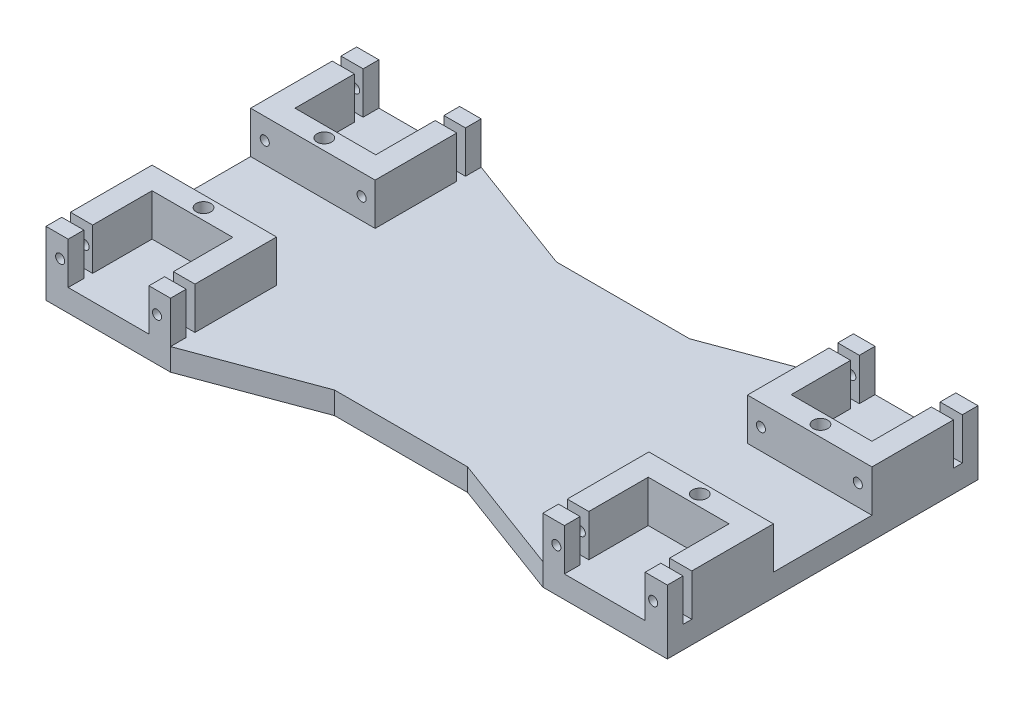
SolidWorks part; units mm, degrees
ref_plane "Front Plane" through (0, 0, 0) normal (0, 0, 1) x (1, 0, 0)
ref_plane "Top Plane" through (0, 0, 0) normal (0, 1, 0) x (1, 0, 0)
ref_plane "Right Plane" through (0, 0, 0) normal (1, 0, 0) x (0, 0, -1)
sketch "Sketch2" plane through (0, 0, 0) normal (0, 1, 0) x (1, 0, 0)
  line L0 (88.9, 0) -> (88.9, 88.9) construction
  line L1 (0, 0) -> (177.8, 0)
  line L2 (0, 0) -> (0, 88.9)
  line L3 (0, 88.9) -> (177.8, 88.9)
  line L4 (177.8, 0) -> (177.8, 88.9)
  line L5 (44.45, 12.7) -> (133.35, 12.7) construction
  line L6 (44.45, 12.7) -> (44.45, 76.2) construction
  line L7 (44.45, 76.2) -> (133.35, 76.2) construction
  line L8 (133.35, 12.7) -> (133.35, 76.2) construction
  line L9 (171.45, 0) -> (148.336, 0)
  line L10 (171.45, 0) -> (171.45, 23.9979)
  line L11 (171.45, 23.9979) -> (148.336, 23.9979)
  line L12 (148.336, 0) -> (148.336, 23.9979)
  line L13 (142.171, 30.3479) -> (177.8, 30.3479)
  line L14 (142.171, 30.3479) -> (142.171, -6.35)
  line L15 (142.171, -6.35) -> (177.8, -6.35)
  line L16 (177.8, 30.3479) -> (177.8, -6.35)
  line L17 (142.171, 30.3479) -> (177.8, -6.35) construction
  line L18 (142.171, -6.35) -> (177.8, 30.3479) construction
  line L19 (0, 44.45) -> (177.8, 44.45) construction
  line L20 (35.629, -6.35) -> (0, -6.35)
  line L21 (0, 30.3479) -> (0, -6.35)
  line L22 (35.629, 30.3479) -> (0, 30.3479)
  line L23 (35.629, 30.3479) -> (35.629, -6.35)
  line L24 (6.35, 23.9979) -> (29.464, 23.9979)
  line L25 (29.464, 0) -> (29.464, 23.9979)
  line L26 (6.35, 0) -> (29.464, 0)
  line L27 (6.35, 0) -> (6.35, 23.9979)
  line L28 (171.45, 64.9021) -> (148.336, 64.9021)
  line L29 (148.336, 88.9) -> (148.336, 64.9021)
  line L30 (171.45, 88.9) -> (148.336, 88.9)
  line L31 (171.45, 88.9) -> (171.45, 64.9021)
  line L32 (142.171, 95.25) -> (177.8, 95.25)
  line L33 (177.8, 58.5521) -> (177.8, 95.25)
  line L34 (142.171, 58.5521) -> (177.8, 58.5521)
  line L35 (142.171, 58.5521) -> (142.171, 95.25)
  line L36 (6.35, 88.9) -> (6.35, 64.9021)
  line L37 (6.35, 88.9) -> (29.464, 88.9)
  line L38 (29.464, 88.9) -> (29.464, 64.9021)
  line L39 (6.35, 64.9021) -> (29.464, 64.9021)
  line L40 (35.629, 58.5521) -> (35.629, 95.25)
  line L41 (35.629, 58.5521) -> (0, 58.5521)
  line L42 (0, 58.5521) -> (0, 95.25)
  line L43 (35.629, 95.25) -> (0, 95.25)
  line L44 (35.629, 0) -> (69.85, 12.7)
  line L45 (69.85, 12.7) -> (107.95, 12.7)
  line L46 (107.95, 12.7) -> (142.171, 0)
  line L47 (35.629, 88.9) -> (69.85, 76.2)
  line L48 (69.85, 76.2) -> (107.95, 76.2)
  line L49 (107.95, 76.2) -> (142.171, 88.9)
  point P9 (159.9855, 11.999)
  dimension "D1" = 88.9
  dimension "D2" = 177.8
  dimension "D3" = 63.5
  dimension "D4" = 88.9
  dimension "D5" = 31.75
  dimension "D6" = 23.114
  dimension ".9448" = 23.9979
  dimension "D7" = 6.35
  dimension "D8" = 6.35
  dimension "D9" = 44.45
  dimension "D10" = 38.1
extrude "Boss-Extrude1" add sketch "Sketch2" along normal blind 6.35 contours L40 L41 L2 L22 L23 L1 L14 L13 L4 L34 L35 L3 | L27 L1 L25 L24 | L1 L27 L24 L25 L23 L22 L2 | L41 L40 L3 L38 L39 L36 L2 | L36 L39 L38 L3 | L31 L3 L29 L28 | L35 L34 L4 L3 L31 L28 L29 | L12 L1 L10 L11 | L13 L14 L1 L12 L11 L10 L4 region at (0.468, 0, -15.174) region at (17.907, 0, -11.999) region at (88.9, 0, -44.45) region at (0.468, 0, -73.726) region at (142.639, 0, -15.174) region at (17.907, 0, -76.901) region at (159.893, 0, -11.999) region at (145.2535, 0, -88.432) region at (159.893, 0, -76.901)
extrude "Boss-Extrude2" add sketch "Sketch2<3>" along normal blind 18.3388 contours L13 L14 L1 L12 L11 L10 L4 | L41 L40 L3 L38 L39 L36 L2 | L35 L34 L4 L3 L31 L28 L29 | L1 L27 L24 L25 L23 L22 L2 region at (0.468, 0, -15.174) region at (0.468, 0, -73.726) region at (142.639, 0, -15.174) region at (145.2535, 0, -88.432)
sketch "Sketch2<3>" plane through (0, 0, 0) normal (0, 1, 0) x (1, 0, 0) same geometry as "Sketch2"
sketch "Sketch3" plane through (0, 18.3388, 0) normal (0, 1, 0) x (1, 0, 0)
  line L0 (142.171, 0) -> (142.171, 30.3479) construction
  line L1 (142.171, 6.9952) -> (177.8, 6.9952)
  line L2 (142.171, 6.9952) -> (142.171, 4.4958)
  line L3 (142.171, 4.4958) -> (177.8, 4.4958)
  line L4 (177.8, 6.9952) -> (177.8, 4.4958)
  line L5 (177.8, 0) -> (177.8, 30.3479) construction
  line L6 (142.171, 0) -> (148.336, 0) construction
  line L8 (88.9, 0) -> (88.9, 88.9) construction
  line L9 (0, 0) -> (177.8, 0) construction
  line L10 (35.629, 4.4958) -> (0, 4.4958)
  line L11 (0, 6.9952) -> (0, 4.4958)
  line L12 (35.629, 6.9952) -> (0, 6.9952)
  line L13 (35.629, 6.9952) -> (35.629, 4.4958)
  line L15 (0, 44.45) -> (177.8, 44.45) construction
  line L16 (35.629, 81.9048) -> (35.629, 84.4042)
  line L17 (35.629, 81.9048) -> (0, 81.9048)
  line L18 (0, 81.9048) -> (0, 84.4042)
  line L19 (35.629, 84.4042) -> (0, 84.4042)
  line L20 (142.171, 84.4042) -> (177.8, 84.4042)
  line L21 (177.8, 81.9048) -> (177.8, 84.4042)
  line L22 (142.171, 81.9048) -> (177.8, 81.9048)
  line L23 (142.171, 81.9048) -> (142.171, 84.4042)
  dimension "D1" = 4.4958
  dimension "D2" = 2.4994
extrude "Cut-Extrude1" cut sketch "Sketch3" against normal up to surface (11.9888 mm away) up to face at (159.893, 6.35, -11.999)
sketch "Sketch4" plane through (0, 0, 0) normal (0, 0, 1) x (1, 0, 0)
  line L0 (148.336, 18.3388) -> (148.336, 6.35) construction
  line L1 (171.45, 18.3388) -> (171.45, 6.35) construction
  line L2 (148.336, 6.35) -> (171.45, 6.35) construction
  line L3 (88.9, 0) -> (88.9, 6.35) construction
  line L6 (69.85, 0) -> (107.95, 0) construction
  line L7 (69.85, 6.35) -> (107.95, 6.35) construction
  circle A0 centre (146.036, 12.3444) radius 1.3005
  circle A1 centre (173.75, 12.3444) radius 1.3005
  circle A4 centre (4.05, 12.3444) radius 1.3005
  circle A5 centre (31.764, 12.3444) radius 1.3005
  dimension "D3" = 2.601
  dimension "D1" = 2.3
  dimension "D2" = 2.3
  dimension "D4" = 5.9944
extrude "Cut-Extrude2" cut sketch "Sketch4" against normal blind 101.346
sketch "Sketch6" plane through (0, 18.3388, 0) normal (0, 1, 0) x (1, 0, 0)
  line L0 (17.907, 23.9979) -> (17.907, 27.1729) construction
  line L1 (6.35, 23.9979) -> (29.464, 23.9979) construction
  line L2 (88.9, 0) -> (88.9, 88.9) construction
  line L3 (88.9, 12.7) -> (88.9, 27.7271) construction
  line L4 (69.85, 12.7) -> (107.95, 12.7) construction
  line L5 (88.9, 44.45) -> (106.0706, 44.45) construction
  line L6 (0, 44.45) -> (177.8, 44.45) construction
  circle A0 centre (17.907, 27.1729) radius 2.1
  circle A1 centre (159.893, 27.1729) radius 2.1
  circle A2 centre (159.893, 61.7271) radius 2.1
  circle A3 centre (17.907, 61.7271) radius 2.1
  dimension "D1" = 4.2
  dimension "D2" = 3.175
extrude "Cut-Extrude3" cut sketch "Sketch6" against normal blind 4.99
